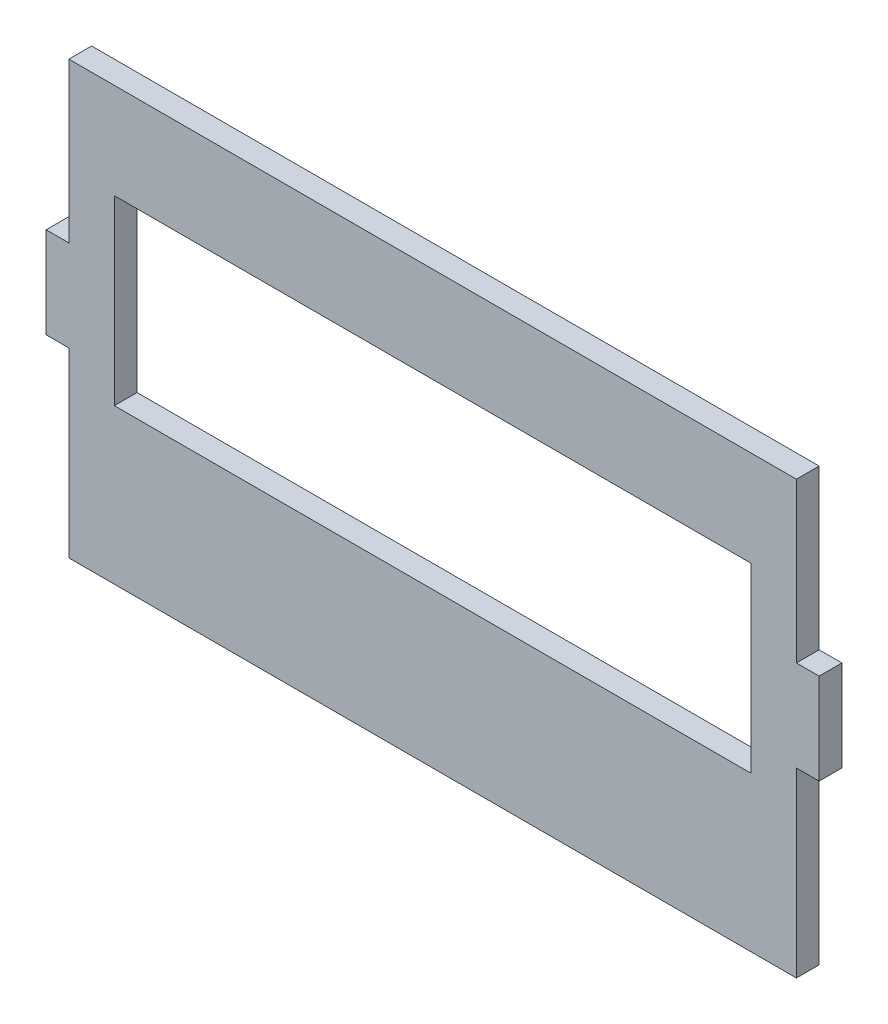
SolidWorks part; units mm, degrees
ref_plane "Front Plane" through (0, 0, 0) normal (0, 0, 1) x (1, 0, 0)
ref_plane "Top Plane" through (0, 0, 0) normal (0, 1, 0) x (1, 0, 0)
ref_plane "Right Plane" through (0, 0, 0) normal (1, 0, 0) x (0, 0, -1)
sketch "Sketch1" plane through (0, 0, 0) normal (0, 0, 1) x (1, 0, 0)
  line L1 (0, 0) -> (101.6, 0)
  line L2 (0, 0) -> (0, 63.5)
  line L3 (0, 63.5) -> (101.6, 63.5)
  line L4 (101.6, 0) -> (101.6, 63.5)
  dimension "D1" = 63.5
  dimension "D2" = 101.6
extrude "Boss-Extrude1" add sketch "Sketch1" along normal blind 3.175
sketch "Sketch2" plane through (0, 0, 3.175) normal (0, 0, 1) x (1, 0, 0)
  line L1 (6.35, 46.99) -> (95.25, 46.99)
  line L2 (6.35, 46.99) -> (6.35, 21.59)
  line L3 (6.35, 21.59) -> (95.25, 21.59)
  line L4 (95.25, 46.99) -> (95.25, 21.59)
  line L5 (0, 63.5) -> (0, 0) construction
  line L8 (0, 0) -> (101.6, 0) construction
  dimension "D1" = 21.59
  dimension "D2" = 88.9
  dimension "D3" = 25.4
  dimension "D4" = 6.35
extrude "Cut-Extrude1" cut sketch "Sketch2" against normal through all
sketch "Sketch3" plane through (0, 0, 3.175) normal (0, 0, 1) x (1, 0, 0)
  line L0 (0, 63.5) -> (0, 0) construction
  line L1 (0, 38.1) -> (-3.175, 38.1)
  line L2 (0, 38.1) -> (0, 25.4)
  line L3 (0, 25.4) -> (-3.175, 25.4)
  line L4 (-3.175, 38.1) -> (-3.175, 25.4)
  line L5 (50.8, 63.5) -> (50.8, 0) construction
  line L6 (101.6, 63.5) -> (0, 63.5) construction
  line L7 (0, 0) -> (101.6, 0) construction
  line L8 (101.6, 25.4) -> (104.775, 25.4)
  line L9 (101.6, 38.1) -> (101.6, 25.4)
  line L10 (101.6, 38.1) -> (104.775, 38.1)
  line L11 (104.775, 38.1) -> (104.775, 25.4)
  point P12 (0, 31.75)
  point P13 (0, 31.75)
  dimension "D1" = 12.7
  dimension "D2" = 3.175
extrude "Boss-Extrude2" add sketch "Sketch3" against normal up to surface (3.175 mm away) up to face at (50.8, 34.29, 0)
sketch "Sketch4" plane through (0, 0, 3.175) normal (0, 0, 1) x (1, 0, 0)
  line L0 (101.6, 38.1) -> (101.6, 63.5) construction
  line L1 (0, 63.5) -> (101.6, 63.5)
  line L2 (0, 63.5) -> (0, 60.325)
  line L3 (0, 60.325) -> (101.6, 60.325)
  line L4 (101.6, 63.5) -> (101.6, 60.325)
  dimension "D1" = 3.175
extrude "Cut-Extrude2" cut sketch "Sketch4" against normal through all
